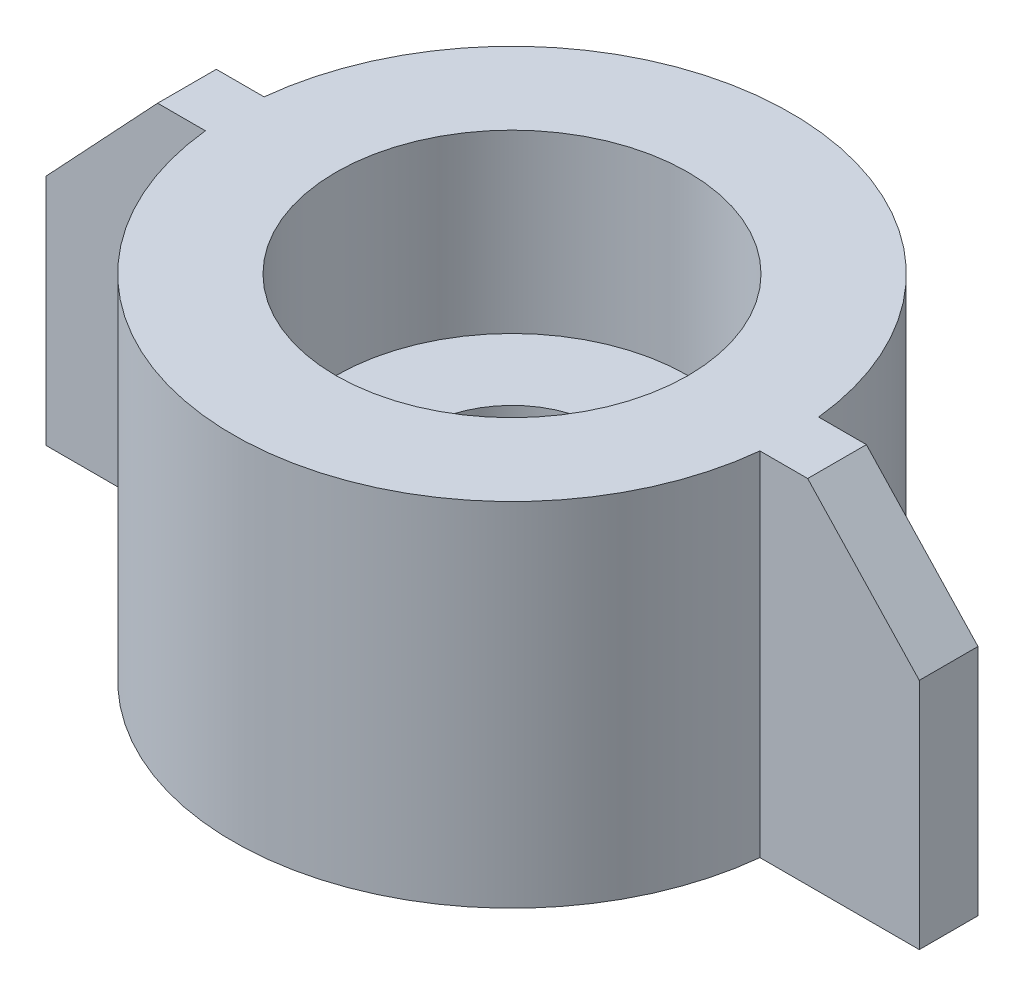
SolidWorks part; units mm, degrees
ref_plane "Ön Düzlem" through (0, 0, 0) normal (0, 0, 1) x (1, 0, 0)
ref_plane "Üst Düzlem" through (0, 0, 0) normal (0, 1, 0) x (1, 0, 0)
ref_plane "Sağ Düzlem" through (0, 0, 0) normal (1, 0, 0) x (0, 0, -1)
sketch "Sketch1" plane through (0, 0, 0) normal (0, 1, 0) x (1, 0, 0)
  circle A0 centre (0, 0) radius 6
  circle A1 centre (0, 0) radius 9.5
  dimension "D1" = 19
  dimension "D2" = 12
extrude "Boss-Extrude1" add sketch "Sketch1" along normal blind 12
sketch "Sketch2" plane through (0, 0, 0) normal (0, 0, 1) x (1, 0, 0)
  line L0 (7.2713, 12) -> (7.2713, 0)
  line L1 (9.5, 12) -> (-9.5, 12) construction
  line L2 (7.2713, 0) -> (14.8767, 0)
  line L3 (14.8767, 0) -> (14.8767, 7.9456)
  line L4 (14.8767, 7.9456) -> (11.074, 12)
  line L5 (11.074, 12) -> (7.2713, 12)
extrude "Boss-Extrude2" add sketch "Sketch2" along normal blind 1 and the other way blind 1
pattern_circular "CirPattern1" count 2 over 360 about axis through (0, 12, 0) along (0, -1, 0) of "Boss-Extrude2"
ref_plane "Plane1" through (0, 4, 0) normal (0, 1, 0) x (1, 0, 0)
sketch "Sketch3" plane through (0, 4, 0) normal (0, 1, 0) x (1, 0, 0)
  circle A0 centre (0, 0) radius 6
  circle A1 centre (0, 0) radius 3
  dimension "D1" = 6
extrude "Boss-Extrude3" add sketch "Sketch3" along normal blind 2
